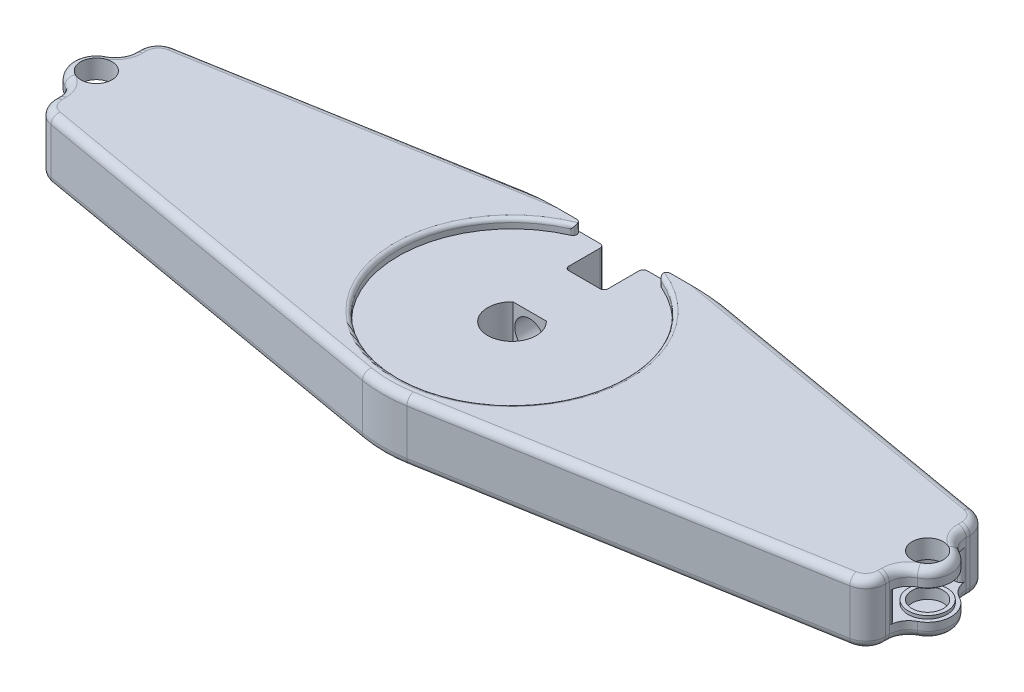
SolidWorks part; units mm, degrees
ref_plane "Front Plane" through (0, 0, 0) normal (0, 0, 1) x (1, 0, 0)
ref_plane "Top Plane" through (0, 0, 0) normal (0, 1, 0) x (1, 0, 0)
ref_plane "Right Plane" through (0, 0, 0) normal (1, 0, 0) x (0, 0, -1)
sketch "Sketch1" plane through (0, 0, 0) normal (0, 1, 0) x (1, 0, 0)
  line L0 (0, 0) -> (-57.07, 0) construction
  line L1 (-53.07, -5.398) -> (-53.07, -4.899)
  line L2 (-50.9992, 7.8609) -> (-2.8328, 16.255)
  line L3 (-50.9992, -7.8609) -> (-2.8328, -16.255)
  line L4 (-53.07, 4.899) -> (-53.07, 5.398)
  line L5 (0, -55) -> (0, 55) construction
  line L6 (53.07, -5.398) -> (53.07, -4.899)
  line L7 (50.9992, -7.8609) -> (2.8328, -16.255)
  line L8 (50.9992, 7.8609) -> (2.8328, 16.255)
  line L9 (53.07, 4.899) -> (53.07, 5.398)
  line L10 (0, 0) -> (0, -3) construction
  line L11 (-2.0396, -2.2) -> (2.0396, -2.2) construction
  line L13 (-2.1325, 2.25) -> (2.1325, 2.25)
  line L14 (-2.0396, 2.2) -> (2.0396, 2.2) construction
  circle A0 centre (-53.07, 0) radius 4 construction
  arc A1 (-54.4336, 2.6722) -> (-54.4336, -2.6722) centre (-53.07, 0) ccw
  arc A2 (2.0396, -2.2) -> (-2.0396, -2.2) centre (0, 0) ccw construction
  arc A3 (-2.8328, -16.255) -> (2.8328, -16.255) centre (0, 0) ccw
  arc A4 (54.4336, 2.6722) -> (54.4336, -2.6722) centre (53.07, 0) cw
  arc A5 (2.8328, -16.255) -> (-2.8328, -16.255) centre (0, 0) cw
  arc A6 (2.8328, 16.255) -> (-2.8328, 16.255) centre (0, 0) ccw
  arc A7 (-2.8328, 16.255) -> (2.8328, 16.255) centre (0, 0) cw
  arc A8 (50.9992, -7.8609) -> (53.07, -5.398) centre (50.57, -5.398) ccw
  arc A9 (54.4336, -2.6722) -> (53.07, -4.899) centre (55.57, -4.899) ccw
  arc A10 (54.4336, 2.6722) -> (53.07, 4.899) centre (55.57, 4.899) cw
  arc A11 (53.07, 5.398) -> (50.9992, 7.8609) centre (50.57, 5.398) ccw
  arc A12 (-53.07, 4.899) -> (-54.4336, 2.6722) centre (-55.57, 4.899) cw
  arc A13 (-54.4336, -2.6722) -> (-53.07, -4.899) centre (-55.57, -4.899) cw
  arc A14 (-53.07, -5.398) -> (-50.9992, -7.8609) centre (-50.57, -5.398) ccw
  arc A15 (-53.07, 5.398) -> (-50.9992, 7.8609) centre (-50.57, 5.398) cw
  arc A17 (-2.0396, -2.2) -> (0, -3) centre (0, 0) ccw construction
  arc A18 (0, -3) -> (2.0396, -2.2) centre (0, 0) ccw construction
  arc A20 (-2.1325, 2.25) -> (2.1325, 2.25) centre (0, 0) ccw
  point P11 (-53.07, 0)
  point P24 (53.07, -7.5)
  point P27 (53.07, -3)
  point P30 (53.07, 3)
  point P33 (53.07, 7.5)
  point P36 (-53.07, 3)
  point P39 (-53.07, -3)
  point P42 (-53.07, -7.5)
  point P45 (-53.07, 7.5)
  point P46 (0, 3)
  point P50 (0, -2.2)
  dimension "D3" = 6
  dimension "D4" = 6
  dimension "D5" = 33
  dimension "D9" = 2.5
  dimension "D12" = 0.1
  dimension "D1" = 57.07
  dimension "D2" = 4
  dimension "D6" = 15
  dimension "D7" = 4.5
  dimension "D8" = 50.9944
  dimension "D10" = 5.2
  dimension "D11" = 0.1
extrude "Boss-Extrude1" add sketch "Sketch1" along normal blind 2 contours A15 L4 A12 A1 A13 L1 A14 L3 A3 L7 A8 L6 A9 A4 A10 L9 A11 L8 A6 L2 A2
sketch "Sketch2" plane through (0, 2, 0) normal (0, 1, 0) x (1, 0, 0)
  circle A0 centre (-53.07, 0) radius 2.5
  circle A1 centre (53.07, 0) radius 2.5
  dimension "D1" = 5
extrude "Boss-Extrude2" add sketch "Sketch2" along normal blind 0.4
sketch "Sketch3" plane through (0, 2.4, 0) normal (0, 1, 0) x (1, 0, 0)
  circle A0 centre (-53.07, 0) radius 2
  circle A1 centre (53.07, 0) radius 2
  dimension "D1" = 4
extrude "Boss-Extrude3" add sketch "Sketch3" along normal blind 3
sketch "Sketch5" plane through (0, 5.4, 0) normal (0, 1, 0) x (1, 0, 0)
  circle A2 centre (-53.07, 0) radius 2.5
  circle A3 centre (-53.07, 0) radius 2.5
  circle A5 centre (53.07, 0) radius 2.5
  circle A6 centre (53.07, 0) radius 2.5
  dimension "D1" = 0
  dimension "D2" = 0
extrude "Boss-Extrude4" add sketch "Sketch5" along normal blind 0.4
sketch "Sketch4" plane through (0, 2, 0) normal (0, 1, 0) x (1, 0, 0)
  line L7 (2.1325, 2.25) -> (-2.1325, 2.25)
  line L8 (2.1325, 2.25) -> (-2.1325, 2.25)
  line L16 (-53.07, 5.398) -> (-53.07, 4.899)
  line L17 (-53.07, -4.899) -> (-53.07, -5.398)
  line L18 (-50.9992, -7.8609) -> (-2.8328, -16.255)
  line L19 (2.8328, -16.255) -> (50.9992, -7.8609)
  line L20 (53.07, -5.398) -> (53.07, -4.899)
  line L21 (53.07, 4.899) -> (53.07, 5.398)
  line L22 (50.9992, 7.8609) -> (2.8328, 16.255)
  line L23 (-2.8328, 16.255) -> (-50.9992, 7.8609)
  line L24 (-53.07, 5.398) -> (-53.07, 4.899)
  line L25 (-53.07, -4.899) -> (-53.07, -5.398)
  line L26 (-50.9992, -7.8609) -> (-2.8328, -16.255)
  line L27 (2.8328, -16.255) -> (50.9992, -7.8609)
  line L28 (53.07, -5.398) -> (53.07, -4.899)
  line L29 (53.07, 4.899) -> (53.07, 5.398)
  line L30 (50.9992, 7.8609) -> (2.8328, 16.255)
  line L31 (-2.8328, 16.255) -> (-50.9992, 7.8609)
  arc A0 (-52.6272, -4.2269) -> (-52.6272, 4.2269) centre (-53.07, 0) ccw
  arc A1 (52.6272, 4.2269) -> (52.6272, -4.2269) centre (53.07, 0) ccw
  arc A7 (-2.1325, 2.25) -> (2.1325, 2.25) centre (0, 0) ccw
  arc A8 (-2.1325, 2.25) -> (2.1325, 2.25) centre (0, 0) ccw
  arc A14 (-52.6272, 4.2269) -> (-53.0742, 4.7533) centre (-52.5751, 4.7241) cw
  arc A15 (-52.6272, -4.2269) -> (-53.0742, -4.7533) centre (-52.5751, -4.7241) ccw
  arc A16 (52.6272, -4.2269) -> (53.0742, -4.7533) centre (52.5751, -4.7241) cw
  arc A17 (53.0742, 4.7533) -> (52.6272, 4.2269) centre (52.5751, 4.7241) cw
  arc A18 (2.8328, 16.255) -> (-2.8328, 16.255) centre (0, 0) ccw
  arc A19 (2.8328, 16.255) -> (-2.8328, 16.255) centre (0, 0) ccw
  arc A26 (-50.9992, 7.8609) -> (-53.07, 5.398) centre (-50.57, 5.398) ccw
  arc A27 (-54.4336, 2.6722) -> (-53.07, 4.899) centre (-55.57, 4.899) ccw
  arc A28 (-54.4336, 2.6722) -> (-54.4336, -2.6722) centre (-53.07, 0) ccw
  arc A29 (-53.07, -4.899) -> (-54.4336, -2.6722) centre (-55.57, -4.899) ccw
  arc A30 (-53.07, -5.398) -> (-50.9992, -7.8609) centre (-50.57, -5.398) ccw
  arc A31 (-2.8328, -16.255) -> (2.8328, -16.255) centre (0, 0) ccw
  arc A32 (50.9992, -7.8609) -> (53.07, -5.398) centre (50.57, -5.398) ccw
  arc A33 (54.4336, -2.6722) -> (53.07, -4.899) centre (55.57, -4.899) ccw
  arc A34 (54.4336, -2.6722) -> (54.4336, 2.6722) centre (53.07, 0) ccw
  arc A35 (53.07, 4.899) -> (54.4336, 2.6722) centre (55.57, 4.899) ccw
  arc A36 (53.07, 5.398) -> (50.9992, 7.8609) centre (50.57, 5.398) ccw
  arc A38 (-50.9992, 7.8609) -> (-53.07, 5.398) centre (-50.57, 5.398) ccw
  arc A39 (-53.0742, 4.7533) -> (-53.07, 4.899) centre (-55.57, 4.899) ccw
  arc A41 (-53.07, -4.899) -> (-53.0742, -4.7533) centre (-55.57, -4.899) ccw
  arc A42 (-53.07, -5.398) -> (-50.9992, -7.8609) centre (-50.57, -5.398) ccw
  arc A43 (-2.8328, -16.255) -> (2.8328, -16.255) centre (0, 0) ccw
  arc A44 (50.9992, -7.8609) -> (53.07, -5.398) centre (50.57, -5.398) ccw
  arc A45 (53.0742, -4.7533) -> (53.07, -4.899) centre (55.57, -4.899) ccw
  arc A47 (53.07, 4.899) -> (53.0742, 4.7533) centre (55.57, 4.899) ccw
  arc A48 (53.07, 5.398) -> (50.9992, 7.8609) centre (50.57, 5.398) ccw
  dimension "D1" = 8.5
  dimension "D2" = 0
  dimension "D3" = 0.5
  dimension "D4" = 0
extrude "Boss-Extrude5" add sketch "Sketch4" along normal up to surface (3.8 mm away) up to face at (-53.07, 5.8, 2.5)
sketch "Sketch6" plane through (0, 5.8, 0) normal (0, 1, 0) x (1, 0, 0)
  line L7 (2.1325, 2.25) -> (-2.1325, 2.25)
  line L8 (2.1325, 2.25) -> (-2.1325, 2.25)
  line L16 (-2.8328, 16.255) -> (-50.9992, 7.8609)
  line L17 (50.9992, 7.8609) -> (2.8328, 16.255)
  line L18 (53.07, 4.899) -> (53.07, 5.398)
  line L19 (53.07, -5.398) -> (53.07, -4.899)
  line L20 (2.8328, -16.255) -> (50.9992, -7.8609)
  line L21 (-50.9992, -7.8609) -> (-2.8328, -16.255)
  line L22 (-53.07, -4.899) -> (-53.07, -5.398)
  line L23 (-53.07, 5.398) -> (-53.07, 4.899)
  line L24 (-2.8328, 16.255) -> (-50.9992, 7.8609)
  line L25 (50.9992, 7.8609) -> (2.8328, 16.255)
  line L26 (53.07, 4.899) -> (53.07, 5.398)
  line L27 (53.07, -5.398) -> (53.07, -4.899)
  line L28 (2.8328, -16.255) -> (50.9992, -7.8609)
  line L29 (-50.9992, -7.8609) -> (-2.8328, -16.255)
  line L30 (-53.07, -4.899) -> (-53.07, -5.398)
  line L31 (-53.07, 5.398) -> (-53.07, 4.899)
  arc A9 (-2.1325, 2.25) -> (2.1325, 2.25) centre (0, 0) ccw
  arc A10 (-2.1325, 2.25) -> (2.1325, 2.25) centre (0, 0) ccw
  arc A14 (2.8328, 16.255) -> (-2.8328, 16.255) centre (0, 0) ccw
  arc A15 (2.8328, 16.255) -> (-2.8328, 16.255) centre (0, 0) ccw
  arc A24 (-50.9992, 7.8609) -> (-53.07, 5.398) centre (-50.57, 5.398) ccw
  arc A26 (53.07, 5.398) -> (50.9992, 7.8609) centre (50.57, 5.398) ccw
  arc A27 (53.07, 4.899) -> (54.4336, 2.6722) centre (55.57, 4.899) ccw
  arc A28 (54.4336, -2.6722) -> (54.4336, 2.6722) centre (53.07, 0) ccw
  arc A29 (54.4336, -2.6722) -> (53.07, -4.899) centre (55.57, -4.899) ccw
  arc A30 (50.9992, -7.8609) -> (53.07, -5.398) centre (50.57, -5.398) ccw
  arc A31 (-2.8328, -16.255) -> (2.8328, -16.255) centre (0, 0) ccw
  arc A32 (-53.07, -5.398) -> (-50.9992, -7.8609) centre (-50.57, -5.398) ccw
  arc A33 (-53.07, -4.899) -> (-54.4336, -2.6722) centre (-55.57, -4.899) ccw
  arc A34 (-54.4336, 2.6722) -> (-54.4336, -2.6722) centre (-53.07, 0) ccw
  arc A35 (-54.4336, 2.6722) -> (-53.07, 4.899) centre (-55.57, 4.899) ccw
  arc A36 (-50.9992, 7.8609) -> (-53.07, 5.398) centre (-50.57, 5.398) ccw
  arc A38 (53.07, 5.398) -> (50.9992, 7.8609) centre (50.57, 5.398) ccw
  arc A39 (53.07, 4.899) -> (54.4336, 2.6722) centre (55.57, 4.899) ccw
  arc A40 (54.4336, -2.6722) -> (54.4336, 2.6722) centre (53.07, 0) ccw
  arc A41 (54.4336, -2.6722) -> (53.07, -4.899) centre (55.57, -4.899) ccw
  arc A42 (50.9992, -7.8609) -> (53.07, -5.398) centre (50.57, -5.398) ccw
  arc A43 (-2.8328, -16.255) -> (2.8328, -16.255) centre (0, 0) ccw
  arc A44 (-53.07, -5.398) -> (-50.9992, -7.8609) centre (-50.57, -5.398) ccw
  arc A45 (-53.07, -4.899) -> (-54.4336, -2.6722) centre (-55.57, -4.899) ccw
  arc A46 (-54.4336, 2.6722) -> (-54.4336, -2.6722) centre (-53.07, 0) ccw
  arc A47 (-54.4336, 2.6722) -> (-53.07, 4.899) centre (-55.57, 4.899) ccw
  dimension "D1" = 0
  dimension "D2" = 0
extrude "Boss-Extrude6" add sketch "Sketch6" along normal blind 2
sketch "Sketch7" plane through (0, 0, 0) normal (0, -1, 0) x (1, 0, 0)
  line L0 (0, -16.255) -> (0, -14.255) construction
  line L5 (-14.309, -14.255) -> (14.309, -14.255)
  line L16 (2.8328, -16.255) -> (50.9992, -7.8609)
  line L17 (-50.9992, -7.8609) -> (-2.8328, -16.255)
  line L18 (-2.8328, -16.255) -> (2.8328, -16.255)
  line L19 (2.8328, -16.255) -> (14.309, -14.255)
  line L20 (-14.309, -14.255) -> (-2.8328, -16.255)
  arc A2 (-2.8328, -16.255) -> (2.8328, -16.255) centre (0, 0) ccw
  arc A3 (-2.8328, -16.255) -> (2.8328, -16.255) centre (0, 0) ccw
  point P8 (0, -14.255)
  dimension "D1" = 2
  dimension "D2" = 0
  dimension "D3" = 0
extrude "Cut-Extrude1" cut sketch "Sketch7" against normal through all
sketch "Sketch8" plane through (0, 0, -14.255) normal (0, 0, -1) x (-1, 0, 0)
  line L0 (0, 3.9) -> (0, 7.8) construction
  line L1 (-14.309, 7.8) -> (14.309, 7.8) construction
  line L2 (0, 3.9) -> (0, 0) construction
  circle A0 centre (0, 3.9) radius 1.9
  dimension "D1" = 3.8
extrude "Cut-Extrude2" cut sketch "Sketch8" against normal up to next
sketch "Sketch9" plane through (0, 7.8, 0) normal (0, 1, 0) x (1, 0, 0)
  circle A0 centre (0, 0) radius 14.5
  point P6 (0, 0)
  dimension "D1" = 29
extrude "Cut-Extrude3" cut sketch "Sketch9" against normal blind 1.2
fillet "Fillet1" radius 0.5 2 edges at (2.6542, 7.2, -14.255) (-2.6542, 7.2, -14.255)
sketch "Sketch10" plane through (0, 0, -14.255) normal (0, 0, -1) x (-1, 0, 0)
  line L6 (-2.5, 6.6) -> (2.5, 6.6)
  line L7 (-5.9833, 6.6) -> (5.9833, 6.6) construction
  line L8 (14.5, 6.6) -> (-14.5, 6.6) construction
  line L9 (2.5, 6.6) -> (2.5, 0)
  line L10 (-14.309, 0) -> (14.309, 0) construction
  line L11 (2.5, 0) -> (-2.5, 0)
  line L12 (-2.5, 0) -> (-2.5, 6.6)
  point P6 (0, 0)
  dimension "D1" = 5
extrude "Cut-Extrude4" cut sketch "Sketch10" against normal blind 5
fillet "Fillet2" radius 0.5 5 edges at (0, 7.8, 14.5) (-2.5, 3.3, -14.255) (-2.5, 3.3, -9.255) (2.5, 3.3, -9.255) (2.5, 3.3, -14.255)
sketch "Sketch12" plane through (0, 0, 0) normal (0, -1, 0) x (1, 0, 0)
  circle A2 centre (-53.07, 0) radius 2
  circle A3 centre (-53.07, 0) radius 2
  circle A5 centre (53.07, 0) radius 2
  circle A6 centre (53.07, 0) radius 2
  dimension "D1" = 0
  dimension "D2" = 0
extrude "Cut-Extrude5" cut sketch "Sketch12" against normal through all from offset 1 offset against normal yes
fillet "Fillet4" radius 1 38 edges at (32.6541, 0, -11.0579) (52.4835, 0, -7.0069) (53.07, 0, -5.1485) (53.438, 0, -3.5934) (-32.6541, 0, -11.0579) (-52.4835, 0, -7.0069) (-53.07, 0, -5.1485) (-53.438, 0, -3.5934) (-56.07, 0, 0) (-53.438, 0, 3.5934) (-53.07, 0, 5.1485) (-52.4835, 0, 7.0069) (-26.916, 0, 12.0579) (0, 0, 16.5) (26.916, 0, 12.0579) (52.4835, 0, 7.0069) (53.07, 0, 5.1485) (53.438, 0, 3.5934) (-32.6541, 7.8, -11.0579) (-52.4835, 7.8, -7.0069) (-53.07, 7.8, -5.1485) (-53.438, 7.8, -3.5934) (-56.07, 7.8, 0) (-53.438, 7.8, 3.5934) (-53.07, 7.8, 5.1485) (-52.4835, 7.8, 7.0069) (-26.916, 7.8, 12.0579) (0, 7.8, 16.5) (26.916, 7.8, 12.0579) (52.4835, 7.8, 7.0069) (53.07, 7.8, 5.1485) (53.438, 7.8, 3.5934) (32.6541, 7.8, -11.0579) (52.4835, 7.8, -7.0069) (53.07, 7.8, -5.1485) (53.438, 7.8, -3.5934) (56.07, 0, 0) (56.07, 7.8, 0)
